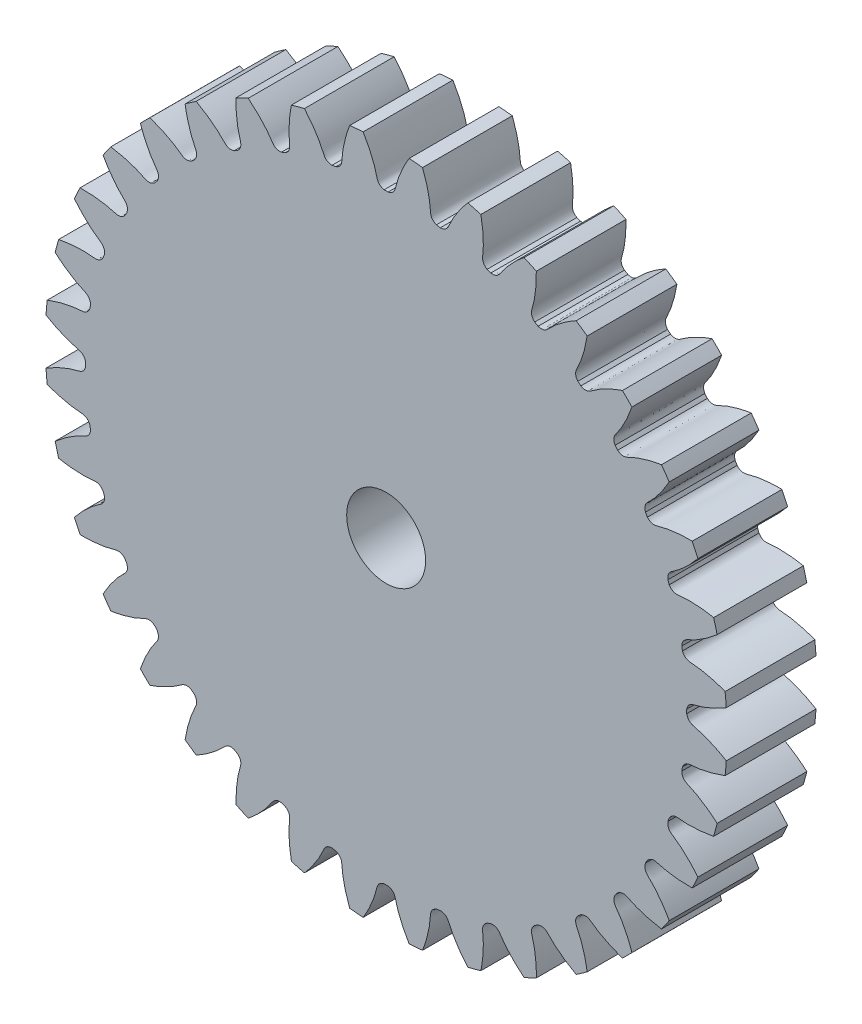
SolidWorks part; units mm, degrees
ref_plane "前视基准面" through (0, 0, 0) normal (0, 0, 1) x (1, 0, 0)
ref_plane "上视基准面" through (0, 0, 0) normal (0, 1, 0) x (1, 0, 0)
ref_plane "右视基准面" through (0, 0, 0) normal (1, 0, 0) x (0, 0, -1)
other "Configuration Table"
sketch "草图1" plane through (0, 0, 0) normal (0, 0, 1) x (1, 0, 0)
  circle A0 centre (0, 0) radius 9.5
extrude "凸台-拉伸1" add sketch "草图1" along normal blind 2.5
ref_axis "基准轴1" through (0, 0, 2.5) along (0, 0, -1)
sketch "草图2" plane through (0, 0, 0) normal (0, 0, 1) x (1, 0, 0)
  line L0 (0, 0) -> (0, 9.5) construction
  circle A0 centre (0, 0) radius 9.5 construction
  arc A1 (0.0549, 8.3748) -> (-0.0549, 8.3748) centre (0, 0) ccw
  arc A2 (1.757, 10.7884) -> (-1.757, 10.7884) centre (0, 0) ccw
  spline S0 degree 3 poles (0.0549, 8.3748) (0.235, 8.4152) (0.2505, 8.5493) (0.2882, 8.6914) (0.2997, 8.7319) (0.3131, 8.7753) (0.3284, 8.8217) (0.3457, 8.871) (0.3652, 8.9231) (0.3869, 8.9779) (0.4111, 9.0354) (0.4378, 9.0956) (0.4671, 9.1582) (0.4992, 9.2232) (0.5341, 9.2907) (0.5719, 9.3603) (0.6128, 9.4322) (0.6569, 9.5061) (0.7043, 9.582) (0.755, 9.6598) (0.8091, 9.7393) (0.8668, 9.8205) (0.9281, 9.9032) (0.9931, 9.9874) (1.0619, 10.0729) (1.1346, 10.1596) (1.2112, 10.2474) (1.2919, 10.3361) (1.3766, 10.4256) (1.4655, 10.5159) (1.5912, 10.6386) (1.6895, 10.7288) (1.757, 10.7884) knots 0 0 0 0 0.120371 0.133303 0.147364 0.162556 0.178878 0.19633 0.214913 0.234626 0.255469 0.277443 0.300547 0.324782 0.350146 0.376641 0.404267 0.433023 0.462909 0.493925 0.526072 0.559349 0.593757 0.629294 0.665963 0.703761 0.74269 0.782749 0.823939 0.866258 0.909709 1 1 1 1
  spline S1 degree 3 poles (-0.0549, 8.3748) (-0.235, 8.4152) (-0.2505, 8.5493) (-0.2882, 8.6914) (-0.2997, 8.7319) (-0.3131, 8.7753) (-0.3284, 8.8217) (-0.3457, 8.871) (-0.3652, 8.9231) (-0.3869, 8.9779) (-0.4111, 9.0354) (-0.4378, 9.0956) (-0.4671, 9.1582) (-0.4992, 9.2232) (-0.5341, 9.2907) (-0.5719, 9.3603) (-0.6128, 9.4322) (-0.6569, 9.5061) (-0.7043, 9.582) (-0.755, 9.6598) (-0.8091, 9.7393) (-0.8668, 9.8205) (-0.9281, 9.9032) (-0.9931, 9.9874) (-1.0619, 10.0729) (-1.1346, 10.1596) (-1.2112, 10.2474) (-1.2919, 10.3361) (-1.3766, 10.4256) (-1.4655, 10.5159) (-1.5912, 10.6386) (-1.6895, 10.7288) (-1.757, 10.7884) knots 0 0 0 0 0.120371 0.133303 0.147364 0.162556 0.178878 0.19633 0.214913 0.234626 0.255469 0.277443 0.300547 0.324782 0.350146 0.376641 0.404267 0.433023 0.462909 0.493925 0.526072 0.559349 0.593757 0.629294 0.665963 0.703761 0.74269 0.782749 0.823939 0.866258 0.909709 1 1 1 1
extrude "切除-拉伸1" cut sketch "草图2" along normal through all
pattern_circular "阵列(圆周)1" count 36 every 10 about axis through (0, 0, 2.5) along (0, 0, -1) of "切除-拉伸1"
sketch "草图4" plane through (0, 0, 0) normal (0, 0, -1) x (-1, 0, 0)
  circle A0 centre (0, 0) radius 1.1
  dimension "D1" = 2.2
extrude "切除-拉伸2" cut sketch "草图4" against normal up to next
